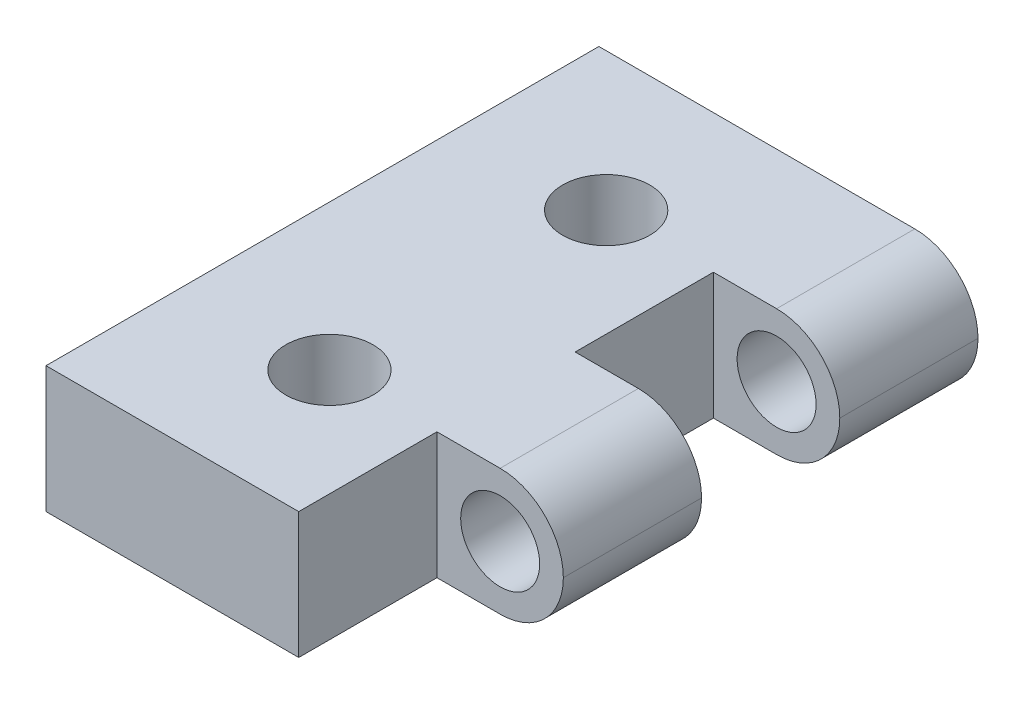
SolidWorks part; units mm, degrees
ref_plane "Front Plane" through (0, 0, 0) normal (0, 0, 1) x (1, 0, 0)
ref_plane "Top Plane" through (0, 0, 0) normal (0, 1, 0) x (1, 0, 0)
ref_plane "Right Plane" through (0, 0, 0) normal (1, 0, 0) x (0, 0, -1)
sketch "Sketch1" plane through (0, 0, 0) normal (0, 1, 0) x (1, 0, 0)
  line L1 (0, 0) -> (15.24, 0)
  line L2 (0, 0) -> (0, 22.225)
  line L3 (0, 22.225) -> (15.24, 22.225)
  line L4 (15.24, 0) -> (15.24, 22.225)
  dimension "D1" = 22.225
  dimension "D2" = 15.24
extrude "Boss-Extrude1" add sketch "Sketch1" along normal blind 5.08
sketch "Sketch3" plane through (0, 0, 0) normal (0, 0, 1) x (1, 0, 0)
  line L3 (0, 5.08) -> (15.24, 5.08) construction
  line L4 (15.24, 5.08) -> (15.24, 0) construction
  circle A0 centre (12.7, 2.54) radius 1.5875
  dimension "D1" = 3.175
  dimension "D2" = 2.54
  dimension "D3" = 2.54
extrude "Cut-Extrude1" cut sketch "Sketch3" against normal through all
fillet "Fillet1" radius 2.54 2 edges at (15.24, 0, -11.1125) (15.24, 5.08, -11.1125)
sketch "Sketch4" plane through (0, 5.08, 0) normal (0, 1, 0) x (1, 0, 0)
  line L0 (0, 0) -> (12.7, 0) construction
  line L1 (10.16, 0) -> (15.24, 0)
  line L2 (10.16, 0) -> (10.16, 5.5562)
  line L3 (10.16, 5.5562) -> (15.24, 5.5562)
  line L4 (15.24, 0) -> (15.24, 5.5562)
  line L5 (15.24, 22.225) -> (15.24, 0) construction
  line L7 (10.16, 11.1125) -> (15.24, 11.1125)
  line L8 (10.16, 11.1125) -> (10.16, 16.6687)
  line L9 (10.16, 16.6687) -> (15.24, 16.6687)
  line L10 (15.24, 11.1125) -> (15.24, 16.6687)
  dimension "D1" = 5.5562
  dimension "D2" = 5.08
  dimension "D3" = 5.5562
  dimension "D4" = 5.5562
  dimension "D5" = 5.08
extrude "Cut-Extrude2" cut sketch "Sketch4" against normal through all
sketch "Sketch5" plane through (0, 5.08, 0) normal (0, 1, 0) x (1, 0, 0)
  line L0 (5.8434, 16.6751) -> (5.8434, 5.5499) construction
  circle A0 centre (5.8434, 16.6751) radius 1.7526
  circle A1 centre (5.8434, 5.5499) radius 1.7526
  point P4 (5.8434, 11.1125)
  dimension "D1" = 3.5052
  dimension "D2" = 3.5052
  dimension "D3" = 11.1252
extrude "Cut-Extrude3" cut sketch "Sketch5" against normal through all
